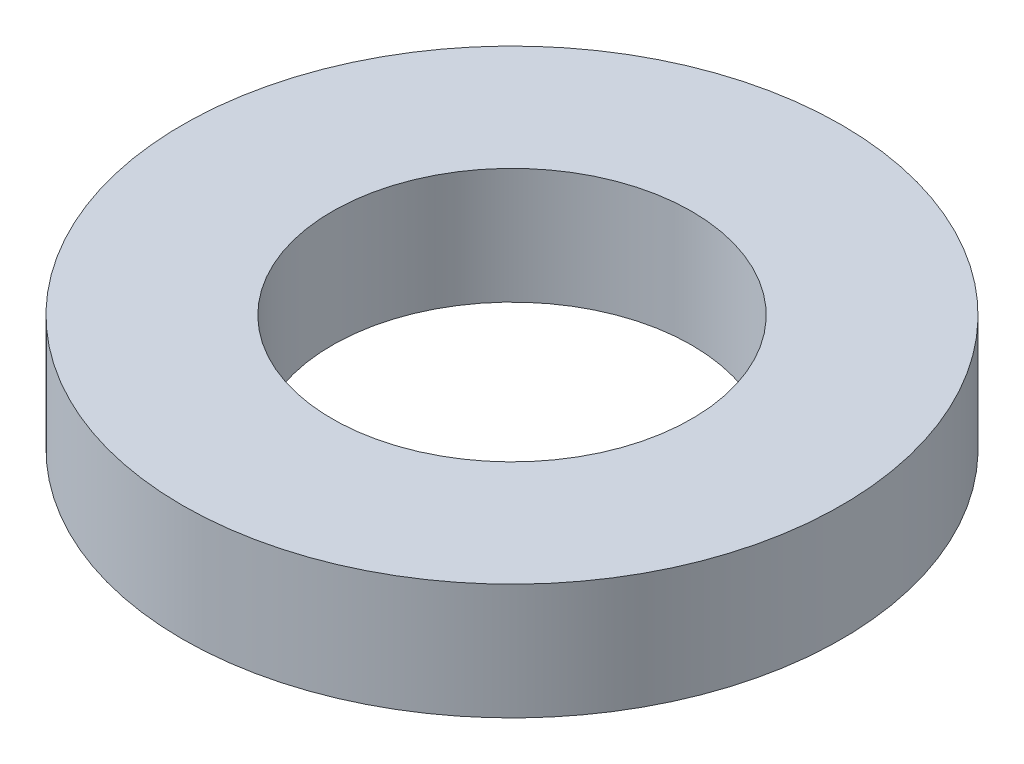
SolidWorks part; units mm, degrees
ref_plane "Front Plane" through (0, 0, 0) normal (0, 0, 1) x (1, 0, 0)
ref_plane "Top Plane" through (0, 0, 0) normal (0, 1, 0) x (1, 0, 0)
ref_plane "Right Plane" through (0, 0, 0) normal (1, 0, 0) x (0, 0, -1)
sketch "Sketch1" plane through (0, 0, 0) normal (0, 1, 0) x (1, 0, 0)
  circle A0 centre (0, 0) radius 82.5
  dimension "FLANGE_OD" = 165
extrude "Boss-Extrude1" add sketch "Sketch1" along normal blind 29
sketch "Sketch2" plane through (0, 0, 0) normal (0, 1, 0) x (1, 0, 0)
  circle A0 centre (0, 0) radius 45
  dimension "BORE_D" = 90
extrude "Cut-Extrude1" cut sketch "Sketch2" along normal through all
sketch "Sketch3" plane through (0, 29, 0) normal (0, 1, 0) x (1, 0, 0)
  circle A0 centre (0, 0) radius 28.5996 construction
  circle A1 centre (-28.5996, 0) radius 3.9758
  dimension "BOLT_D" = 7.9516
  dimension "BOLT_PCD" = 57.1992
extrude "Cut-Extrude2" cut sketch "Sketch3" against normal blind 18.8582 rebuild error yes
pattern_circular "CirPattern1" count 8 over 360 rebuild error yes
